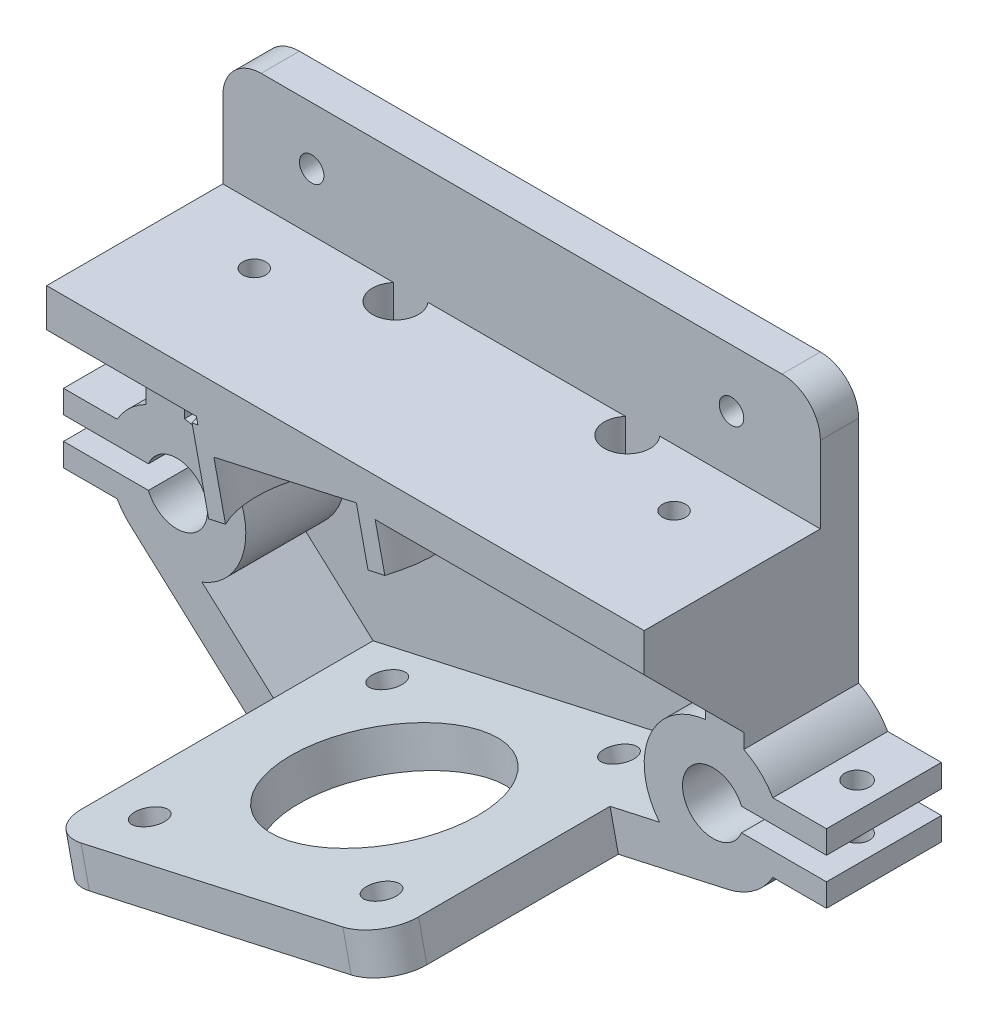
SolidWorks part; units mm, degrees
ref_plane "Front Plane" through (0, 0, 0) normal (0, 0, 1) x (1, 0, 0)
ref_plane "Top Plane" through (0, 0, 0) normal (0, 1, 0) x (1, 0, 0)
ref_plane "Right Plane" through (0, 0, 0) normal (1, 0, 0) x (0, 0, -1)
sketch "Sketch1" plane through (0, 0, 0) normal (0, 0, 1) x (1, 0, 0)
  line L0 (0, -1000) -> (0, 49000) construction
  line L1 (-39, 28) -> (39, 28)
  line L2 (39, 28) -> (39, 8.0623)
  line L3 (36.951, -8.786) -> (-23.8235, -22.2816)
  line L4 (-39, 28) -> (-39, 8.0623)
  line L6 (-34, 23) -> (34, 23)
  line L7 (34, 23) -> (34, 8.9443)
  line L9 (-15.1232, 54.2651) -> (10823.8083, -48756.3581) construction
  line L10 (-1035, 0) -> (48965, 0) construction
  line L11 (-34, 23) -> (-34, 8.9443)
  line L12 (-22.3817, -16.8397) -> (-31.7139, -8.3786)
  line L13 (-23.8235, -22.2816) -> (-41.0451, -6.6675)
  line L14 (27.9966, -5.6526) -> (-22.3817, -16.8397)
  line L15 (-49.7942, 4.5) -> (-42.7942, 4.5)
  line L16 (-49.7942, 4.5) -> (-49.7942, 1.5)
  line L17 (-49.7942, 1.5) -> (-38.7081, 1.5)
  line L18 (42.7942, 4.5) -> (49.7942, 4.5)
  line L19 (-49.7942, -1.5) -> (-38.7081, -1.5)
  line L20 (-49.7942, -1.5) -> (-49.7942, -4.5)
  line L21 (-49.7942, -4.5) -> (-42.7942, -4.5)
  line L23 (38.7081, 1.5) -> (49.7942, 1.5)
  line L24 (49.7942, 4.5) -> (49.7942, 1.5)
  line L25 (38.7081, -1.5) -> (49.7942, -1.5)
  line L27 (42.7942, -4.5) -> (49.7942, -4.5)
  line L28 (49.7942, -1.5) -> (49.7942, -4.5)
  arc A0 (-38.7081, -1.5) -> (-38.7081, 1.5) centre (-35, 0) ccw
  arc A1 (38.7081, 1.5) -> (38.7081, -1.5) centre (35, 0) ccw
  arc A2 (34, 8.9443) -> (27.9966, -5.6526) centre (35, 0) ccw
  arc A3 (-39, 8.0623) -> (-42.7942, 4.5) centre (-35, 0) ccw
  arc A4 (-42.7942, -4.5) -> (-41.0451, -6.6675) centre (-35, 0) ccw
  arc A5 (-31.7139, -8.3786) -> (-34, 8.9443) centre (-35, 0) ccw
  arc A6 (36.951, -8.786) -> (42.7942, -4.5) centre (35, 0) ccw
  arc A8 (42.7942, 4.5) -> (39, 8.0623) centre (35, 0) ccw
  dimension "D1" = 8
  dimension "D2" = 70
  dimension "D4" = 18
  dimension "D5" = 19
  dimension "D14" = 9
  dimension "D3" = 102.52
  dimension "D6" = 5
  dimension "D7" = 5
  dimension "D8" = 3
  dimension "D9" = 3
  dimension "D10" = 22.5
  dimension "D11" = 5
  dimension "D12" = 5
  dimension "D13" = 3
  dimension "D15" = 7
  dimension "D16" = 3
  dimension "D17" = 7
  dimension "D18" = 5
  dimension "D19" = 90
  dimension "D20" = 3
extrude "Boss-Extrude1" add sketch "Sketch1" along normal blind 15
sketch "Sketch2" plane through (0, -4.5, 0) normal (0, -1, 0) x (1, 0, 0)
  line L2 (-46.2942, -985) -> (-46.2942, 49015) construction
  line L3 (-49.7942, 15) -> (-42.7942, 15) construction
  line L4 (46.2942, -985) -> (46.2942, 49015) construction
  line L5 (42.7942, 15) -> (49.7942, 15) construction
  line L6 (-1049.7942, 7.5) -> (48950.2058, 7.5) construction
  line L7 (-49.7942, 15) -> (-49.7942, 0) construction
  circle A0 centre (-46.2942, 7.5) radius 1.6
  circle A1 centre (46.2942, 7.5) radius 1.6
  point P13 (-46.2942, 15)
  point P14 (46.2942, 15)
  point P19 (-49.7942, 7.5)
  dimension "D1" = 3.2
extrude "Cut-Extrude1" cut sketch "Sketch2" against normal through all
sketch "Sketch3" plane through (0, 0, 15) normal (0, 0, 1) x (1, 0, 0)
  line L0 (-22.3817, -16.8397) -> (-21.2978, -21.7208)
  line L1 (-23.8235, -22.2816) -> (36.951, -8.786) construction
  line L2 (22.6321, -11.9657) -> (21.5482, -7.0846)
  line L3 (-22.3817, -16.8397) -> (27.9966, -5.6526) construction
  line L4 (-22.3817, -16.8397) -> (21.5482, -7.0846)
  line L5 (-21.2978, -21.7208) -> (22.6321, -11.9657)
  dimension "D1" = 45
extrude "Boss-Extrude2" add sketch "Sketch3" along normal blind 30
fillet "Fillet1" radius 5 3 edges at (-23.8235, -22.2816, 7.5) (22.0902, -9.5251, 45) (-21.8398, -19.2802, 45)
sketch "Sketch4" plane through (3.5958, -16.1929, 0) normal (0.2168, -0.9762, 0) x (0.9762, 0.2168, 0)
  line L0 (-991.2843, 22.5) -> (49008.7157, 22.5) construction
  line L1 (-3, -955) -> (-3, 49045) construction
  line L2 (-20.5, 45) -> (14.5, 45) construction
  line L3 (-25.5, 0) -> (34.1677, 0) construction
  line L5 (-24.15, 43.65) -> (18.15, 43.65) construction
  line L6 (-24.15, 43.65) -> (-24.15, 1.35) construction
  line L7 (-24.15, 1.35) -> (18.15, 1.35) construction
  line L8 (18.15, 43.65) -> (18.15, 1.35) construction
  line L9 (-24.15, 43.65) -> (18.15, 1.35) construction
  line L10 (-24.15, 1.35) -> (18.15, 43.65) construction
  circle A0 centre (-3, 22.5) radius 12.5
  circle A1 centre (-18.5, 38) radius 2
  circle A2 centre (12.5, 38) radius 2
  circle A3 centre (12.5, 7) radius 2
  circle A4 centre (-18.5, 7) radius 2
  point P7 (-3, 45)
  dimension "D1" = 25
  dimension "D2" = 4
  dimension "D3" = 31
  dimension "D4" = 31
  dimension "D5" = 42.3
  dimension "D6" = 42.3
extrude "Cut-Extrude2" cut sketch "Sketch4" against normal up to next
sketch "Sketch5" plane through (0, 0, 0) normal (0, 0, -1) x (-1, 0, 0)
  line L0 (-34, 23) -> (-34, 8.9443)
  line L1 (-34, 8.9443) -> (-27.9966, -5.6526)
  line L2 (-27.9966, -5.6526) -> (22.3817, -16.8397)
  line L3 (22.3817, -16.8397) -> (31.7139, -8.3786)
  line L4 (31.7139, -8.3786) -> (29.2519, 2.8465)
  line L5 (29.2519, 2.8465) -> (34, 8.9443)
  line L6 (34, 8.9443) -> (34, 23)
  line L7 (34, 23) -> (-34, 23)
extrude "Boss-Extrude3" add sketch "Sketch5" against normal blind 2
sketch "Sketch6" plane through (0, 0, 2) normal (0, 0, 1) x (1, 0, 0)
  line L0 (3.0875, 23) -> (4.3882, 17.1427)
  line L1 (-34, 23) -> (34, 23) construction
  line L2 (-19.4484, 23) -> (-17.0887, 12.3735)
  line L3 (4.3882, 17.1427) -> (-17.0887, 12.3735)
  line L4 (-19.4484, 23) -> (3.0875, 23)
  line L5 (16.6671, -8.1685) -> (-17.5006, -15.7558) construction
  line L6 (-15.8471, 57.5251) -> (10823.1725, -48753.4947) construction
  dimension "D1" = 22
  dimension "D2" = 6
extrude "Boss-Extrude4" add sketch "Sketch6" along normal blind 26
sketch "Sketch7" plane through (0, 23, 0) normal (0, 1, 0) x (1, 0, 0)
  line L1 (39, -28) -> (-39, -28)
  line L2 (39, -28) -> (39, -15)
  line L3 (39, -15) -> (-39, -15)
  line L4 (-39, -28) -> (-39, -15)
  line L5 (39, -15) -> (39, 0) construction
  line L6 (-39, -15) -> (-39, 0) construction
  line L7 (39, -15) -> (-39, -15) construction
  line L8 (3.0875, -28) -> (-19.4484, -28) construction
extrude "Boss-Extrude5" add sketch "Sketch7" along normal blind 5
sketch "Sketch8" plane through (-3.4216, 15.4084, 0) normal (0.2168, -0.9762, 0) x (0.9762, 0.2168, 0)
  line L0 (-14.7792, 28) -> (-12.5263, 28)
  line L1 (-14, 28) -> (8, 28) construction
  line L2 (6.5263, 28) -> (8.7792, 28)
  arc A0 (-12.5263, 28) -> (6.5263, 28) centre (-3, 22.5) ccw
  arc A1 (-14.7792, 28) -> (8.7792, 28) centre (-3, 22.5) ccw
  dimension "D1" = 22
  dimension "D2" = 26
extrude "Boss-Extrude6" add sketch "Sketch8" against normal blind 10
sketch "Sketch9" plane through (-3.4216, 15.4084, 0) normal (0.2168, -0.9762, 0) x (0.9762, 0.2168, 0)
  circle A0 centre (-3, 22.5) radius 11
  arc A1 (-12.5263, 28) -> (6.5263, 28) centre (-3, 22.5) ccw construction
extrude "Cut-Extrude4" cut sketch "Sketch9" against normal blind 7
chamfer "Chamfer1" distance 13 angle 45 2 edges at (-36.5, 23, 15) (36.5, 23, 15)
sketch "Sketch10" plane through (0, 28, 0) normal (0, 1, 0) x (1, 0, 0)
  line L0 (-39, -28) -> (-39, 0) construction
  line L1 (39, 0) -> (-39, 0)
  line L2 (39, 0) -> (39, -5)
  line L3 (39, -5) -> (-39, -5)
  line L4 (-39, 0) -> (-39, -5)
  dimension "D1" = 5
extrude "Boss-Extrude7" add sketch "Sketch10" along normal blind 15
sketch "Sketch11" plane through (0, 0, 5) normal (0, 0, 1) x (1, 0, 0)
  line L0 (-961, 35.5) -> (49039, 35.5) construction
  line L1 (39, 43) -> (39, 28) construction
  line L2 (-39, 43) -> (-39, 28) construction
  circle A0 centre (-27.4, 35.5) radius 1.6
  circle A1 centre (27.4, 35.5) radius 1.6
  point P9 (39, 35.5)
  dimension "D1" = 3.2
  dimension "D2" = 10
  dimension "D3" = 10
extrude "Cut-Extrude5" cut sketch "Sketch11" against normal through all
sketch "Sketch12" plane through (0, 28, 0) normal (0, 1, 0) x (1, 0, 0)
  line L0 (-955.9714, -12.5) -> (49044.0286, -12.5) construction
  line L1 (-39, -5) -> (39, -5) construction
  line L2 (39, -28) -> (39, -5) construction
  line L3 (-39, -28) -> (-39, -5) construction
  circle A0 centre (27.4, -12.5) radius 1.5
  circle A1 centre (-27.4, -12.5) radius 1.5
  dimension "D2" = 3
  dimension "D3" = 11.6
  dimension "D4" = 11.6
  dimension "D1" = 7.5
extrude "Cut-Extrude6" cut sketch "Sketch12" against normal up to next
fillet "Fillet2" radius 5 2 edges at (-39, 43, 2.5) (39, 43, 2.5)
sketch "Sketch14" plane through (0, 28, 0) normal (0, 1, 0) x (1, 0, 0)
  line L0 (18.0346, -5) -> (13.5625, -5)
  line L2 (-12.2282, -5) -> (-16.7003, -5)
  line L3 (-39, -5) -> (39, -5) construction
  arc A0 (13.5625, -5) -> (18.0346, -5) centre (15.7986, -7) ccw
  arc A1 (-16.7003, -5) -> (-12.2282, -5) centre (-14.4643, -7) ccw
  dimension "D1" = 6
extrude "Cut-Extrude7" cut sketch "Sketch14" against normal up to next
